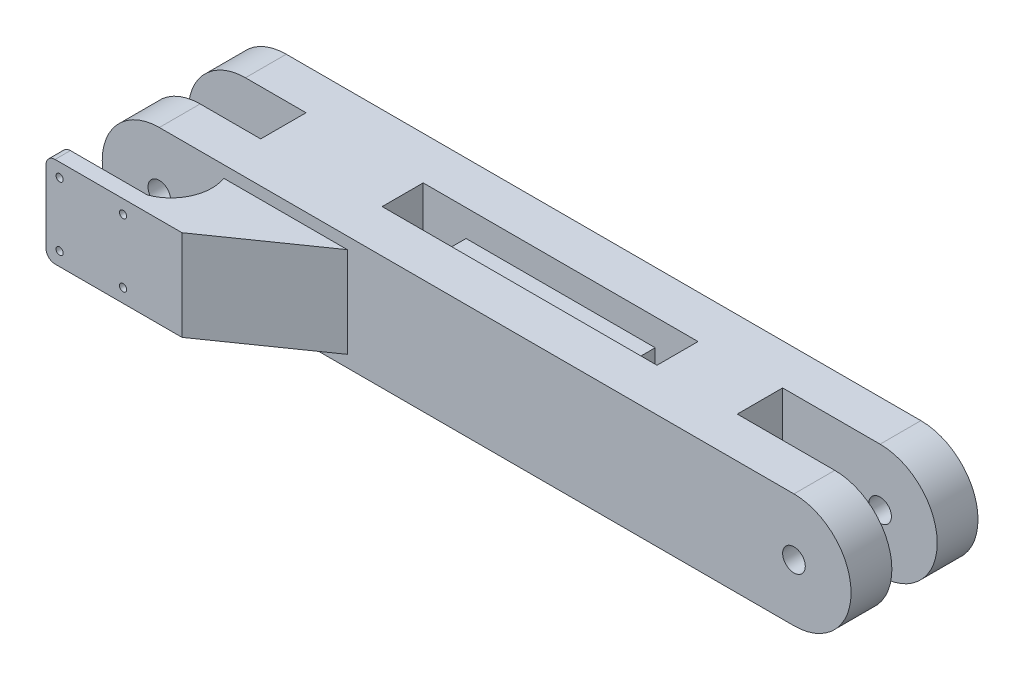
SolidWorks part; units mm, degrees
ref_plane "Front" through (0, 0, 0) normal (0, 0, 1) x (1, 0, 0)
ref_plane "Top" through (0, 0, 0) normal (0, 1, 0) x (1, 0, 0)
ref_plane "Right" through (0, 0, 0) normal (1, 0, 0) x (0, 0, -1)
sketch "Sketch1" plane through (0, 0, 0) normal (0, 0, 1) x (1, 0, 0)
  line L0 (-47.2174, -8.0761) -> (130.5826, -8.0761) construction
  line L1 (-47.2174, 7.9239) -> (130.5826, 7.9239)
  line L2 (-47.2174, -24.0761) -> (130.5826, -24.0761)
  arc A0 (-47.2174, 7.9239) -> (-47.2174, -24.0761) centre (-47.2174, -8.0761) ccw
  arc A1 (130.5826, -24.0761) -> (130.5826, 7.9239) centre (130.5826, -8.0761) ccw
  circle A2 centre (-47.2174, -8.0761) radius 3.175
  circle A3 centre (130.5826, -8.0761) radius 3.175
  point P2 (41.6826, -8.0761)
  dimension "D1" = 16
  dimension "D3" = 6.35
  dimension "D4" = 6.35
  dimension "D2" = 177.8
extrude "Boss-Extrude1" add sketch "Sketch1" along normal blind 11.43
sketch "Sketch2" plane through (0, 0, 11.43) normal (0, 0, 1) x (1, 0, 0)
  line L2 (-39.1367, -24.0761) -> (-39.1367, 7.9239)
  line L4 (130.5826, 7.9239) -> (-47.2174, 7.9239) construction
  line L7 (-47.2174, -24.0761) -> (130.5826, -24.0761) construction
  line L9 (122.3276, -24.0761) -> (122.3276, 7.9239)
  line L10 (-39.1367, 7.9239) -> (122.3276, 7.9239)
  line L11 (-39.1367, -24.0761) -> (122.3276, -24.0761)
  point P13 (-39.1367, -8.0761)
  point P16 (16.9972, 0.4239)
  point P24 (122.3276, -8.0761)
extrude "Boss-Extrude2" add sketch "Sketch2" along normal blind 12.7
sketch "Sketch5" plane through (0, 0, 24.13) normal (0, 0, 1) x (1, 0, 0)
  line L0 (-47.2174, -8.0761) -> (130.5826, -8.0761) construction
  line L1 (-47.2174, 7.9239) -> (130.5826, 7.9239)
  line L2 (-47.2174, -24.0761) -> (130.5826, -24.0761)
  arc A0 (-47.2174, 7.9239) -> (-47.2174, -24.0761) centre (-47.2174, -8.0761) ccw
  arc A1 (130.5826, -24.0761) -> (130.5826, 7.9239) centre (130.5826, -8.0761) ccw
  circle A2 centre (-47.2174, -8.0761) radius 3.175
  circle A3 centre (130.5826, -8.0761) radius 3.175
  point P4 (41.6826, -8.0761)
  dimension "D1" = 16
  dimension "D2" = 6.35
  dimension "D3" = 6.35
extrude "Boss-Extrude3" add sketch "Sketch5" along normal blind 11.43
sketch "Sketch6" plane through (0, 7.9239, 0) normal (0, 1, 0) x (1, 0, 0)
  line L0 (41.6826, 0) -> (41.6826, -35.56)
  line L1 (130.5826, 0) -> (-47.2174, 0) construction
  line L2 (130.5826, -35.56) -> (-47.2174, -35.56) construction
  line L3 (-39.1367, -17.78) -> (122.3276, -17.78)
  line L4 (-39.1367, -24.13) -> (-39.1367, -11.43) construction
  line L5 (122.3276, -24.13) -> (122.3276, -11.43) construction
  line L7 (3.1826, -23.53) -> (80.1826, -23.53)
  line L8 (3.1826, -23.53) -> (3.1826, -12.03)
  line L9 (3.1826, -12.03) -> (80.1826, -12.03)
  line L10 (80.1826, -23.53) -> (80.1826, -12.03)
  line L11 (3.1826, -23.53) -> (80.1826, -12.03) construction
  line L12 (3.1826, -12.03) -> (80.1826, -23.53) construction
  point P12 (41.6826, -17.78)
extrude "Cut-Extrude1" cut sketch "Sketch6" against normal blind 7.5 contours L7 L10 L9 L8
sketch "Sketch7" plane through (0, 0.4239, 0) normal (0, 1, 0) x (1, 0, 0)
  line L5 (3.1826, -23.53) -> (80.1826, -23.53) construction
  line L10 (3.1826, -12.03) -> (15.1826, -12.03)
  line L11 (3.1826, -12.03) -> (3.1826, -23.53)
  line L12 (3.1826, -23.53) -> (15.1826, -23.53)
  line L13 (15.1826, -12.03) -> (15.1826, -23.53)
  line L14 (3.1826, -12.03) -> (80.1826, -12.03) construction
  line L15 (80.1826, -23.53) -> (68.1826, -23.53)
  line L16 (80.1826, -23.53) -> (80.1826, -12.03)
  line L17 (80.1826, -12.03) -> (68.1826, -12.03)
  line L18 (68.1826, -23.53) -> (68.1826, -12.03)
sketch "Sketch10" plane through (0, 0, 35.56) normal (0, 0, 1) x (1, 0, 0)
  line L0 (-47.2174, -24.0761) -> (130.5826, -24.0761) construction
  line L1 (-34.5174, -20.7761) -> (-57.3774, -20.7761)
  line L3 (-34.5174, 4.6239) -> (-57.3774, 4.6239)
  line L4 (-59.9174, -18.2361) -> (-59.9174, 2.0839)
  line L5 (-34.5174, -20.7761) -> (-59.9174, 4.6239) construction
  line L6 (-34.5174, 4.6239) -> (-59.9174, -20.7761) construction
  line L7 (-34.5174, 4.6239) -> (-21.8174, 4.6239)
  line L9 (-34.5174, -20.7761) -> (-21.8174, -20.7761)
  line L10 (-21.8174, 4.6239) -> (-21.8174, -20.7761)
  arc A1 (-57.3774, -20.7761) -> (-59.9174, -18.2361) centre (-57.3774, -18.2361) cw
  arc A2 (-57.3774, 4.6239) -> (-59.9174, 2.0839) centre (-57.3774, 2.0839) ccw
  dimension "D1" = 2.54
  dimension "D2" = 35.56
  dimension "D3" = 25.4
  dimension "D4" = 12.7
  dimension "D5" = 3.3
extrude "Boss-Extrude4" add sketch "Sketch10" along normal blind 19.05 contours L4 A2 L3 L7 L10 L9 L1 A1
sketch "Sketch14" plane through (0, 4.6239, 0) normal (0, 1, 0) x (1, 0, 0)
  line L0 (-59.9174, -35.56) -> (-29.1834, -35.56)
  line L1 (-56.9493, -35.56) -> (-21.8174, -35.56) construction
  line L2 (-59.9174, -35.56) -> (-59.9174, -50.3102)
  line L3 (-59.9174, -54.61) -> (-59.9174, -35.56) construction
  line L4 (-59.9174, -50.3102) -> (-35.7956, -50.3102)
  arc A0 (-29.1834, -35.56) -> (-35.7956, -50.3102) centre (-39.8646, -39.629) cw
  dimension "D1" = 11.43
  dimension "D2" = 24.1218
  dimension "D3" = 14.7502
  dimension "D4" = 30.734
extrude "Cut-Extrude3" cut sketch "Sketch14" against normal blind 30.48
sketch "Sketch15" plane through (0, -20.7761, 0) normal (0, -1, 0) x (1, 0, 0)
  line L0 (-21.8174, 35.56) -> (5.4637, 35.56)
  line L1 (-47.2174, 35.56) -> (130.5826, 35.56) construction
  line L2 (-21.8174, 54.61) -> (5.4637, 35.56)
  line L3 (-21.8174, 54.61) -> (-21.8174, 35.56)
extrude "Boss-Extrude5" add sketch "Sketch15" against normal blind 25.4
extrude "Cut-Extrude4" cut sketch "Sketch7" against normal blind 50.8 contours L18 L17 L16 L15
extrude "Cut-Extrude5" cut sketch "Sketch7<5>" against normal blind 50.8 contours L13 L12 L11 L10
sketch "Sketch7<5>" plane through (0, 0.4239, 0) normal (0, 1, 0) x (1, 0, 0) same geometry as "Sketch7"
sketch "Sketch16" plane through (-39.1367, 0, 0) normal (-1, 0, 0) x (0, 0, 1)
  line L1 (11.43, 7.9239) -> (24.13, 7.9239)
  line L2 (11.43, 7.9239) -> (11.43, -24.0761)
  line L3 (11.43, -24.0761) -> (24.13, -24.0761)
  line L4 (24.13, 7.9239) -> (24.13, -24.0761)
extrude "Cut-Extrude6" cut sketch "Sketch16" against normal blind 8.89
sketch "Sketch17" plane through (0, 0, 50.3102) normal (0, 0, -1) x (-1, 0, 0)
  line L0 (47.2174, 4.6239) -> (47.2174, -20.7761) construction
  line L1 (57.3774, 4.6239) -> (35.7956, 4.6239) construction
  line L2 (35.7956, -20.7761) -> (57.3774, -20.7761) construction
  line L3 (35.7868, -8.0761) -> (59.9174, -8.0761) construction
  line L4 (59.9174, -18.2361) -> (59.9174, 2.0839) construction
  circle A0 centre (47.2174, -8.0761) radius 3.175 construction
  circle A1 centre (47.2174, -8.0761) radius 3.175
  circle A2 centre (56.1074, 0.8139) radius 1
  circle A3 centre (56.1074, -16.9661) radius 1
  circle A4 centre (38.3274, -16.9661) radius 1
  circle A5 centre (38.3274, 0.8139) radius 1
  dimension "D3" = 2
  dimension "D1" = 17.78
  dimension "D2" = 17.78
extrude "Cut-Extrude7" cut sketch "Sketch17" against normal up to surface (4.2998 mm away) contours A5 | A2 | A3 | A4 region at (-56.1074, 0.8139, 50.3102) region at (-56.1074, -16.9661, 50.3102) region at (-38.3274, 0.8139, 50.3102) up to face at (-46.5461, -8.0761, 54.61)
sketch "Sketch18" plane through (122.3276, 0, 0) normal (1, 0, 0) x (0, 0, -1)
  line L1 (-24.13, 7.9239) -> (-11.43, 7.9239)
  line L2 (-24.13, 7.9239) -> (-24.13, -24.0761)
  line L3 (-24.13, -24.0761) -> (-11.43, -24.0761)
  line L4 (-11.43, 7.9239) -> (-11.43, -24.0761)
extrude "Cut-Extrude8" cut sketch "Sketch18" against normal blind 19.05
sketch "Sketch19" plane through (0, 0, 0) normal (0, 0, -1) x (-1, 0, 0)
  line L1 (-130.5826, -1.477) -> (-136.2976, -4.7765)
  line L2 (-136.2976, -4.7765) -> (-136.2976, -11.3756)
  line L3 (-136.2976, -11.3756) -> (-130.5826, -14.6752)
  line L4 (-130.5826, -14.6752) -> (-124.8676, -11.3756)
  line L5 (-124.8676, -11.3756) -> (-124.8676, -4.7765)
  line L6 (-124.8676, -4.7765) -> (-130.5826, -1.477)
  circle A0 centre (-130.5826, -8.0761) radius 5.715 construction
extrude "Cut-Extrude9" cut sketch "Sketch19" against normal blind 3.81
